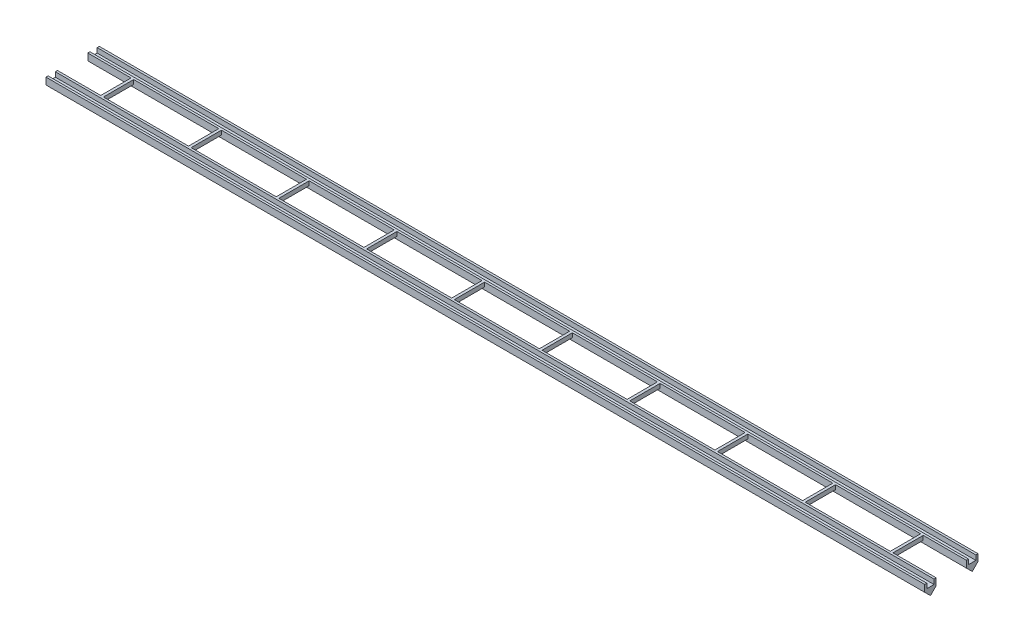
SolidWorks part; units mm, degrees
ref_plane "Front Plane" through (0, 0, 0) normal (0, 0, 1) x (1, 0, 0)
ref_plane "Top Plane" through (0, 0, 0) normal (0, 1, 0) x (1, 0, 0)
ref_plane "Right Plane" through (0, 0, 0) normal (1, 0, 0) x (0, 0, -1)
sketch "Sketch1" plane through (0, 0, 0) normal (1, 0, 0) x (0, 0, -1)
  line L0 (0, 0) -> (0, 50000) construction
  line L1 (5.2539, 0) -> (5.2539, -2.367)
  line L2 (5.2539, -2.367) -> (7.25, -4.3631)
  line L3 (8.5, 0) -> (9.2461, 0)
  line L4 (8.5, -1.6493) -> (8.5, 0)
  line L5 (9.2461, -2.367) -> (7.25, -4.3631)
  line L6 (9.2461, 0) -> (9.2461, -2.367)
  line L7 (8.5, -1.6493) -> (6, -1.6493)
  line L8 (6, -1.6493) -> (6, 0)
  line L9 (6, 0) -> (5.2539, 0)
  line L10 (7.25, -1.3683) -> (7.25, 49998.6317) construction
  line L11 (-7.25, -1.3683) -> (-7.25, 49998.6317) construction
  line L12 (-6, 0) -> (-5.2539, 0)
  line L13 (-6, -1.6493) -> (-6, 0)
  line L14 (-8.5, -1.6493) -> (-6, -1.6493)
  line L15 (-9.2461, 0) -> (-9.2461, -2.367)
  line L16 (-9.2461, -2.367) -> (-7.25, -4.3631)
  line L17 (-8.5, -1.6493) -> (-8.5, 0)
  line L18 (-8.5, 0) -> (-9.2461, 0)
  line L19 (-5.2539, -2.367) -> (-7.25, -4.3631)
  line L20 (-5.2539, 0) -> (-5.2539, -2.367)
  dimension "D1" = 2.5
  dimension "D2" = 12
extrude "Boss-Extrude1" add sketch "Sketch1" along normal blind 304.8
sketch "Sketch2" plane through (0, 0, -5.2539) normal (0, 0, 1) x (1, 0, 0)
  line L0 (304.8, 0) -> (0, 0) construction
  line L1 (15, 0) -> (15.9221, 0)
  line L2 (15, 0) -> (15, -1.478)
  line L3 (15, -1.478) -> (15.9221, -1.478) construction
  line L4 (15.9221, 0) -> (15.9221, -1.478)
  line L5 (15, -1.478) -> (15.4611, -1.939)
  line L6 (15.4611, -1.939) -> (15.9221, -1.478)
  line L7 (45.4309, 0) -> (46.353, 0)
  line L8 (45.4309, 0) -> (45.4309, -1.478)
  line L9 (46.353, 0) -> (46.353, -1.478)
  line L10 (45.4309, -1.478) -> (45.8919, -1.939)
  line L11 (45.8919, -1.939) -> (46.353, -1.478)
  line L12 (45.4309, -1.478) -> (46.353, -1.478) construction
  line L13 (75.8617, 0) -> (76.7839, 0)
  line L14 (75.8617, 0) -> (75.8617, -1.478)
  line L15 (76.7839, 0) -> (76.7839, -1.478)
  line L16 (75.8617, -1.478) -> (76.3228, -1.939)
  line L17 (76.3228, -1.939) -> (76.7839, -1.478)
  line L18 (75.8617, -1.478) -> (76.7839, -1.478) construction
  line L19 (106.2926, 0) -> (107.2148, 0)
  line L20 (106.2926, 0) -> (106.2926, -1.478)
  line L21 (107.2148, 0) -> (107.2148, -1.478)
  line L22 (106.2926, -1.478) -> (106.7537, -1.939)
  line L23 (106.7537, -1.939) -> (107.2148, -1.478)
  line L24 (106.2926, -1.478) -> (107.2148, -1.478) construction
  line L25 (136.7235, 0) -> (137.6456, 0)
  line L26 (136.7235, 0) -> (136.7235, -1.478)
  line L27 (137.6456, 0) -> (137.6456, -1.478)
  line L28 (136.7235, -1.478) -> (137.1846, -1.939)
  line L29 (137.1846, -1.939) -> (137.6456, -1.478)
  line L30 (136.7235, -1.478) -> (137.6456, -1.478) construction
  line L31 (167.1544, 0) -> (168.0765, 0)
  line L32 (167.1544, 0) -> (167.1544, -1.478)
  line L33 (168.0765, 0) -> (168.0765, -1.478)
  line L34 (167.1544, -1.478) -> (167.6154, -1.939)
  line L35 (167.6154, -1.939) -> (168.0765, -1.478)
  line L36 (167.1544, -1.478) -> (168.0765, -1.478) construction
  line L37 (0, 0) -> (0, -2.367) construction
  line L39 (197.5852, 0) -> (198.5074, 0)
  line L40 (197.5852, 0) -> (197.5852, -1.478)
  line L41 (198.5074, 0) -> (198.5074, -1.478)
  line L42 (197.5852, -1.478) -> (198.0463, -1.939)
  line L43 (198.0463, -1.939) -> (198.5074, -1.478)
  line L44 (197.5852, -1.478) -> (198.5074, -1.478) construction
  line L45 (228.0161, 0) -> (228.9383, 0)
  line L46 (228.0161, 0) -> (228.0161, -1.478)
  line L47 (228.9383, 0) -> (228.9383, -1.478)
  line L48 (228.0161, -1.478) -> (228.4772, -1.939)
  line L49 (228.4772, -1.939) -> (228.9383, -1.478)
  line L50 (228.0161, -1.478) -> (228.9383, -1.478) construction
  line L51 (258.447, 0) -> (259.3691, 0)
  line L52 (258.447, 0) -> (258.447, -1.478)
  line L53 (259.3691, 0) -> (259.3691, -1.478)
  line L54 (258.447, -1.478) -> (258.9081, -1.939)
  line L55 (258.9081, -1.939) -> (259.3691, -1.478)
  line L56 (258.447, -1.478) -> (259.3691, -1.478) construction
  line L57 (288.8779, 0) -> (289.8, 0)
  line L58 (288.8779, 0) -> (288.8779, -1.478)
  line L59 (289.8, 0) -> (289.8, -1.478)
  line L60 (288.8779, -1.478) -> (289.3389, -1.939)
  line L61 (289.3389, -1.939) -> (289.8, -1.478)
  line L62 (288.8779, -1.478) -> (289.8, -1.478) construction
  line L63 (304.8, 0) -> (304.8, -2.367) construction
  dimension "D2" = 15
  dimension "D3" = 15
  dimension "D1" = 10
extrude "Boss-Extrude2" add sketch "Sketch2" along normal up to next
equation "\"D3@Sketch2\"=\"D2@Sketch2\""
